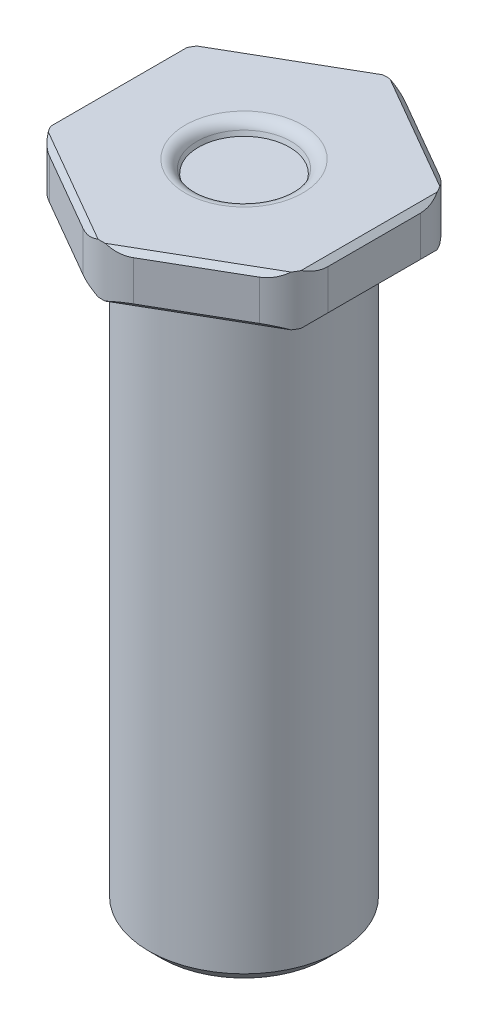
SolidWorks part; units mm, degrees
ref_plane "Front Plane" through (0, 0, 0) normal (0, 0, 1) x (1, 0, 0)
ref_plane "Top Plane" through (0, 0, 0) normal (0, 1, 0) x (1, 0, 0)
ref_plane "Right Plane" through (0, 0, 0) normal (1, 0, 0) x (0, 0, -1)
sketch "Sketch2" plane through (0, 0, 0) normal (0, 1, 0) x (1, 0, 0)
  circle A0 centre (0, 0) radius 9.652
  dimension "D1" = 19.304
extrude "Boss-Extrude1" add sketch "Sketch2" along normal blind 63.5
chamfer "Chamfer1" distance 1.27 angle 45 1 edges at (0, 0, 9.652)
ref_plane "Plane1" through (0, 1.27, 0) normal (0, -1, 0) x (-1, 0, 0)
sketch "Sketch6" plane through (0, 63.5, 0) normal (0, 1, 0) x (1, 0, 0)
  line L1 (0, 15.24) -> (-13.1982, 7.62)
  line L2 (-13.1982, 7.62) -> (-13.1982, -7.62)
  line L3 (-13.1982, -7.62) -> (0, -15.24)
  line L4 (0, -15.24) -> (13.1982, -7.62)
  line L5 (13.1982, -7.62) -> (13.1982, 7.62)
  line L6 (13.1982, 7.62) -> (0, 15.24)
  circle A0 centre (0, 0) radius 13.1982 construction
  dimension "D1" = 15.24
extrude "Boss-Extrude2" add sketch "Sketch6" along normal mid plane 5.08
chamfer "Chamfer2" distance 0.508 angle 45 12 edges at (13.1982, 66.04, 0) (6.5991, 66.04, 11.43) (-6.5991, 66.04, 11.43) (-13.1982, 66.04, 0) (-6.5991, 66.04, -11.43) (6.5991, 66.04, -11.43) (6.5991, 60.96, -11.43) (-6.5991, 60.96, -11.43) (13.1982, 60.96, 0) (6.5991, 60.96, 11.43) (-13.1982, 60.96, 0) (-6.5991, 60.96, 11.43)
fillet "Fillet1" radius 5.08 6 edges at (-13.1982, 63.5, -7.62) (-13.1982, 63.5, 7.62) (0, 63.5, -15.24) (13.1982, 63.5, -7.62) (13.1982, 63.5, 7.62) (0, 63.5, 15.24)
sketch "Sketch7" plane through (0, 66.04, 0) normal (0, 1, 0) x (1, 0, 0)
  circle A0 centre (0, 0) radius 5.08
  dimension "D1" = 10.16
extrude "Cut-Extrude1" cut sketch "Sketch7" against normal blind 1.27 draft 20
fillet "Fillet2" radius 1.27 1 edges at (0, 66.04, 5.08)
